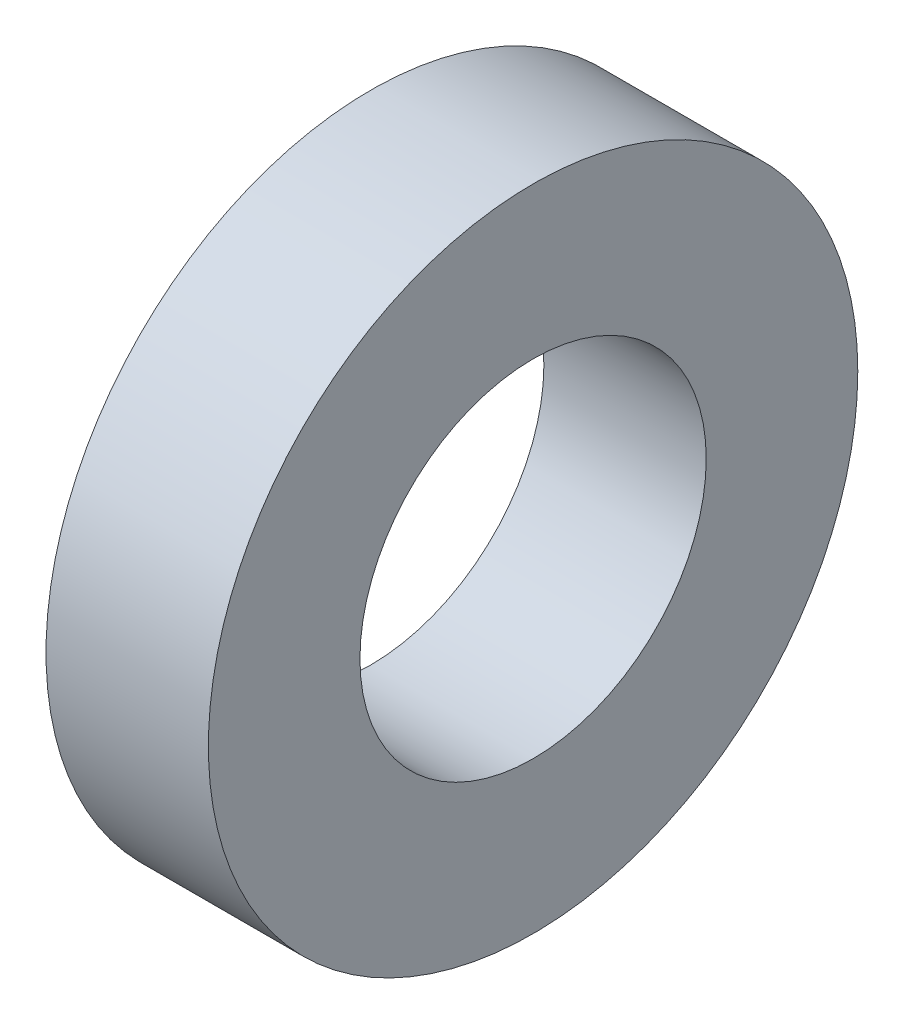
SolidWorks part; units mm, degrees
ref_plane "Front Plane" through (0, 0, 0) normal (0, 0, 1) x (1, 0, 0)
ref_plane "Top Plane" through (0, 0, 0) normal (0, 1, 0) x (1, 0, 0)
ref_plane "Right Plane" through (0, 0, 0) normal (1, 0, 0) x (0, 0, -1)
sketch "Sketch1" plane through (0, 0, 0) normal (1, 0, 0) x (0, 0, -1)
  circle A0 centre (0, 0) radius 12
  circle A1 centre (0, 0) radius 6.3987
  dimension "D1" = 24
extrude "Boss-Extrude1" add sketch "Sketch1" along normal blind 6
